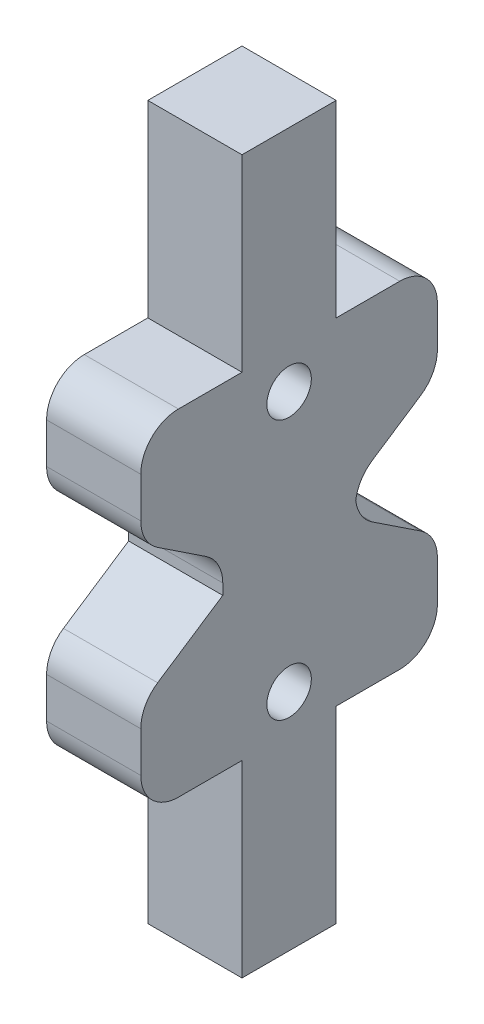
SolidWorks part; units mm, degrees
ref_plane "Front Plane" through (0, 0, 0) normal (0, 0, 1) x (1, 0, 0)
ref_plane "Top Plane" through (0, 0, 0) normal (0, 1, 0) x (1, 0, 0)
ref_plane "Right Plane" through (0, 0, 0) normal (1, 0, 0) x (0, 0, -1)
sketch "Sketch1" plane through (0, 0, 0) normal (1, 0, 0) x (0, 0, -1)
  line L0 (10, 24.952) -> (10, 0) construction
  line L1 (0, 0) -> (6.825, 0)
  line L2 (0, 0) -> (0, 6.6296)
  line L3 (0, 22.666) -> (6.825, 22.666)
  line L4 (20, 0) -> (20, 6.6296)
  line L5 (0, 16.0364) -> (5.5285, 12.3776)
  line L6 (6.825, -12.7) -> (13.175, -12.7)
  line L7 (6.825, -12.7) -> (6.825, 0)
  line L9 (13.175, -12.7) -> (13.175, 0)
  line L10 (6.825, -12.7) -> (13.175, 0) construction
  line L11 (6.825, 0) -> (13.175, -12.7) construction
  line L12 (5.5285, 12.3776) -> (5.5285, 10.2884)
  line L13 (5.5285, 10.2884) -> (0, 6.6296)
  line L14 (0, 16.0364) -> (0, 22.666)
  line L15 (14.4715, 10.2884) -> (20, 6.6296)
  line L16 (14.4715, 12.3776) -> (14.4715, 10.2884)
  line L17 (20, 16.0364) -> (14.4715, 12.3776)
  line L18 (20, 16.0364) -> (20, 22.666)
  line L19 (13.175, 0) -> (20, 0)
  line L20 (14.4715, 11.333) -> (5.5285, 11.333) construction
  line L21 (6.825, 35.366) -> (6.825, 22.666)
  line L22 (6.825, 35.366) -> (13.175, 35.366)
  line L23 (13.175, 35.366) -> (13.175, 22.666)
  line L24 (13.175, 22.666) -> (20, 22.666)
  circle A0 centre (10, 19.952) radius 1.4999
  circle A1 centre (10, 2.426) radius 1.4999
  point P7 (10, -6.35)
  dimension "D5" = 2.714
  dimension "D6" = 17.526
  dimension "D7" = 2.9997
  dimension "D8" = 2.9997
  dimension "D1" = 20
  dimension "D2" = 22.666
  dimension "D3" = 12.7
  dimension "D4" = 6.35
extrude "Boss-Extrude1" add sketch "Sketch1" along normal blind 6.35
fillet "Fillet1" radius 2.54 11 edges at (3.175, 12.3776, -14.4715) (3.175, 16.0364, -20) (3.175, 10.2884, -14.4715) (3.175, 6.6296, -20) (3.175, 0, -20) (3.175, 0, 0) (3.175, 6.6296, 0) (3.175, 12.3776, -5.5285) (3.175, 16.0364, 0) (3.175, 22.666, 0) (3.175, 22.666, -20)
